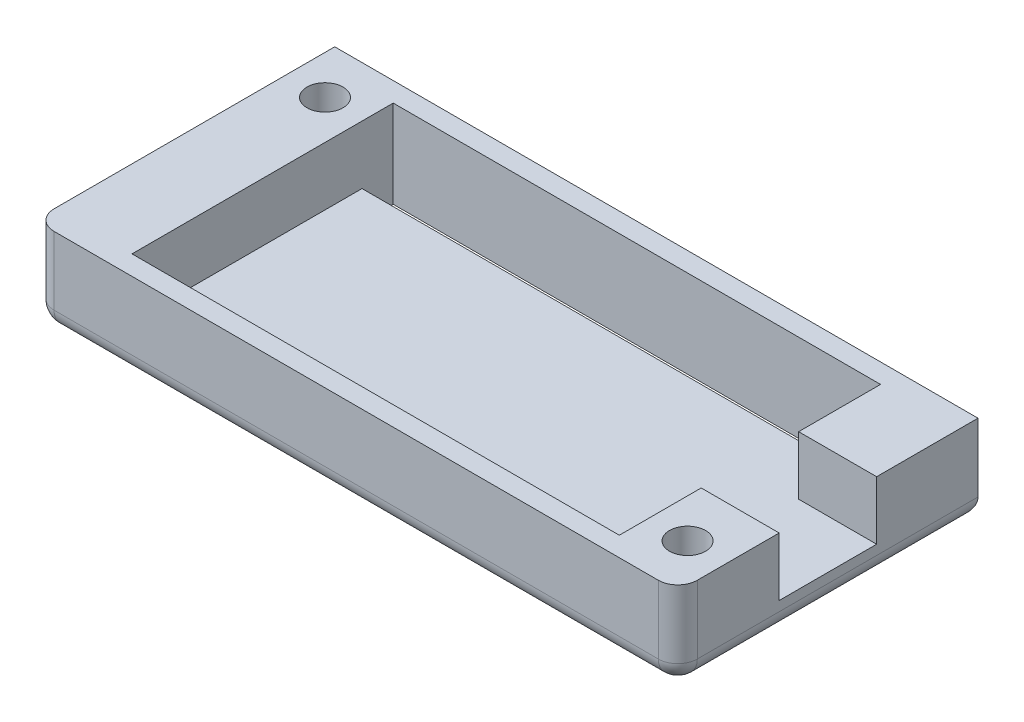
SolidWorks part; units mm, degrees
ref_plane "Front Plane" through (0, 0, 0) normal (0, 0, 1) x (1, 0, 0)
ref_plane "Top Plane" through (0, 0, 0) normal (0, 1, 0) x (1, 0, 0)
ref_plane "Right Plane" through (0, 0, 0) normal (1, 0, 0) x (0, 0, -1)
sketch "Sketch1" plane through (0, 0, 0) normal (0, 1, 0) x (1, 0, 0)
  line L1 (0, 0) -> (66, 0)
  line L2 (0, 0) -> (0, 30.8)
  line L3 (0, 30.8) -> (66, 30.8)
  line L4 (66, 0) -> (66, 30.8)
  line L5 (8, 28.8) -> (58, 28.8)
  line L6 (8, 28.8) -> (8, 25.6)
  line L7 (8, 25.6) -> (58, 25.6)
  line L8 (58, 28.8) -> (58, 25.6)
  line L9 (8, 5.2) -> (58, 5.2)
  line L10 (8, 5.2) -> (8, 2)
  line L11 (8, 2) -> (58, 2)
  line L12 (58, 5.2) -> (58, 2)
  dimension "D1" = 50
  dimension "D3" = 3.2
  dimension "D4" = 3.2
  dimension "D5" = 26.8
  dimension "D6" = 2
  dimension "D7" = 2
  dimension "D8" = 8
  dimension "D10" = 8
extrude "Boss-Extrude1" add sketch "Sketch1" along normal blind 3
sketch "Sketch2" plane through (0, 3, 0) normal (0, 1, 0) x (1, 0, 0)
  line L1 (8, 28.8) -> (58, 28.8)
  line L2 (8, 28.8) -> (8, 2)
  line L3 (8, 2) -> (58, 2)
  line L4 (58, 28.8) -> (58, 2)
  line L5 (0, 30.8) -> (66, 30.8)
  line L6 (0, 30.8) -> (0, 0)
  line L7 (0, 0) -> (66, 0)
  line L8 (66, 30.8) -> (66, 0)
extrude "Boss-Extrude2" add sketch "Sketch2" along normal blind 6
sketch "Sketch3" plane through (0, 9, 0) normal (0, 1, 0) x (1, 0, 0)
  line L1 (66, 0) -> (66, 30.8) construction
  line L2 (0, 30.8) -> (0, 0) construction
  line L3 (0, 0) -> (66, 0) construction
  line L4 (66, 30.8) -> (0, 30.8) construction
  circle A0 centre (62, 5) radius 1.85
  circle A1 centre (4, 25.8) radius 1.85
  dimension "D1" = 3.7
  dimension "D2" = 4
  dimension "D3" = 4
  dimension "D4" = 5
  dimension "D5" = 5
extrude "Cut-Extrude1" cut sketch "Sketch3" against normal through all
fillet "Fillet1" radius 2 6 edges at (33, 0, -30.8) (66, 0, -15.4) (0, 0, -15.4) (33, 0, 0) (66, 4.5, 0) (0, 4.5, 0)
sketch "Sketch4" plane through (0, 9, 0) normal (0, 1, 0) x (1, 0, 0)
  line L0 (58, 2) -> (58, 28.8) construction
  line L1 (58, 20.4) -> (66, 20.4)
  line L2 (58, 20.4) -> (58, 10.4)
  line L3 (58, 10.4) -> (66, 10.4)
  line L4 (66, 20.4) -> (66, 10.4)
  line L5 (66, 2) -> (66, 30.8) construction
  line L8 (66, 30.8) -> (0, 30.8) construction
  dimension "D1" = 10
  dimension "D2" = 10.4
extrude "Cut-Extrude2" cut sketch "Sketch4" against normal up to surface (6 mm away) up to face at (33, 3, -15.4)
